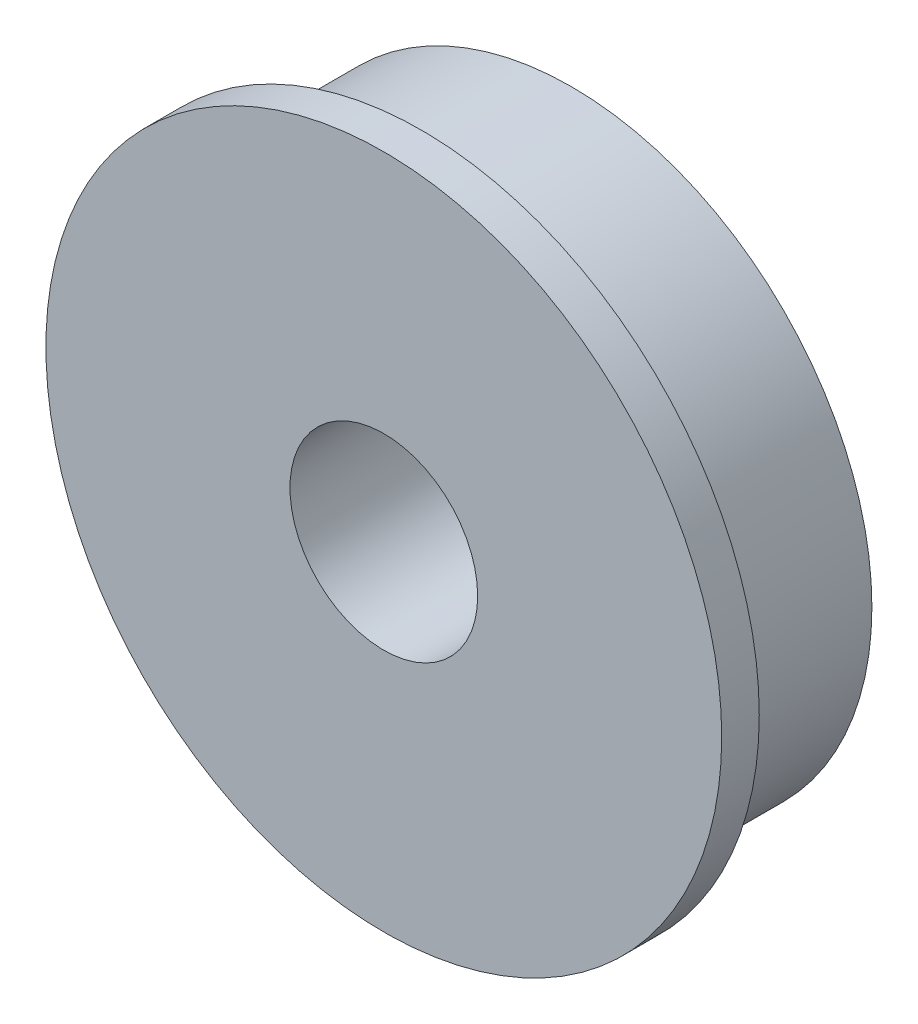
SolidWorks part; units mm, degrees
ref_plane "Płaszczyzna przednia" through (0, 0, 0) normal (0, 0, 1) x (1, 0, 0)
ref_plane "Płaszczyzna górna" through (0, 0, 0) normal (0, 1, 0) x (1, 0, 0)
ref_plane "Płaszczyzna prawa" through (0, 0, 0) normal (1, 0, 0) x (0, 0, -1)
sketch "Szkic1" plane through (0, 0, 0) normal (0, 0, 1) x (1, 0, 0)
  circle A0 centre (0, 0) radius 2.5
  circle A1 centre (0, 0) radius 8
extrude "Dodanie-wyciągnięcie1" add sketch "Szkic1" along normal blind 5
sketch "Szkic2" plane through (0, 0, 5) normal (0, 0, 1) x (1, 0, 0)
  circle A0 centre (0, 0) radius 8
  circle A1 centre (0, 0) radius 9
extrude "Dodanie-wyciągnięcie2" add sketch "Szkic2" against normal blind 1
